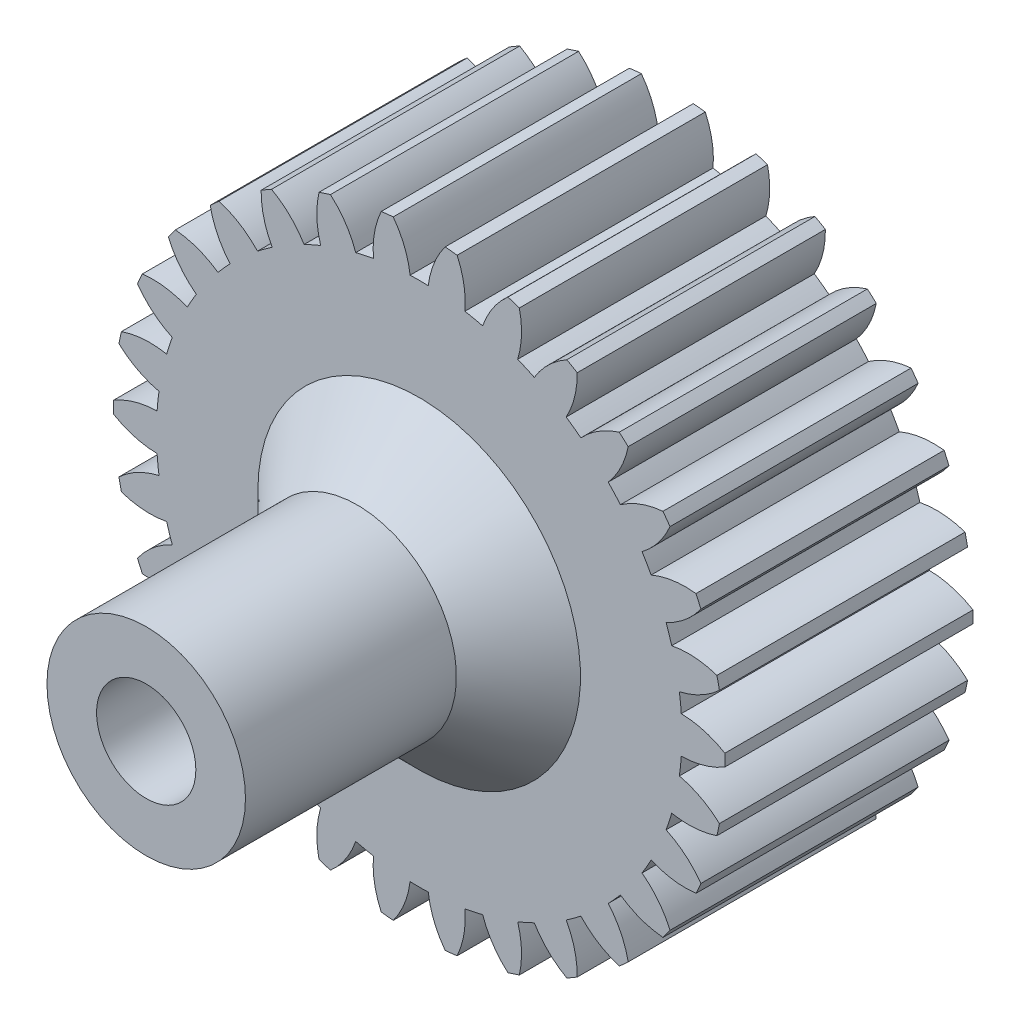
SolidWorks part; units mm, degrees
ref_plane "Front" through (0, 0, 0) normal (0, 0, 1) x (1, 0, 0)
ref_plane "Top" through (0, 0, 0) normal (0, 1, 0) x (1, 0, 0)
ref_plane "Right" through (0, 0, 0) normal (1, 0, 0) x (0, 0, -1)
sketch "Эскиз1" plane through (0, 0, 0) normal (0, 0, 1) x (1, 0, 0)
  circle A0 centre (0, 0) radius 10.5875 construction
  circle A1 centre (0, 0) radius 11.5 construction
  circle A2 centre (0, 0) radius 12.32
  circle A3 centre (0, 0) radius 10.805 construction
  dimension "D1" = 21.175
  dimension "D2" = 23
  dimension "D3" = 24.64
  dimension "D4" = 21.61
extrude "Бобышка-Вытянуть1" add sketch "Эскиз1" along normal mid plane 10
sketch "Эскиз2" plane through (0, 0, 5) normal (0, 0, 1) x (1, 0, 0)
  line L0 (-0.9448, 15.1928) -> (0, 0) construction
  line L1 (-0.7321, 11.7723) -> (-4.9391, 9.6101) construction
  line L2 (-0.6, 11.4843) -> (0.6, 11.4843) construction
  line L3 (0, 0) -> (0, 12.32) construction
  circle A0 centre (0, 0) radius 12.32 construction
  circle A1 centre (0, 0) radius 10.805 construction
  arc A2 (-1.4587, 12.7367) -> (-0.3658, 10.5812) centre (-3.8896, 10.1495) cw
  circle A3 centre (0, 0) radius 10.5875 construction
  circle A4 centre (0, 0) radius 11.5 construction
  arc A5 (1.4587, 12.7367) -> (0.3658, 10.5812) centre (3.8896, 10.1495) ccw
  arc A6 (-0.3658, 10.5812) -> (0.3658, 10.5812) centre (0, 0) cw
  circle A8 centre (0, 0) radius 12.82
  arc A9 (1.4587, 12.7367) -> (-1.4587, 12.7367) centre (0, 0) ccw
  point P3 (-0.7321, 11.7723)
  dimension "D1" = 0.525
  dimension "D2" = 1.2
  dimension "D3" = 4.7301
  dimension "D4" = 1.18
  dimension "D5" = 0.5
sketch "Эскиз4" plane through (0, 0, 0) normal (0, 1, 0) x (1, 0, 0)
  line L0 (0, 5) -> (0, -5)
  line L1 (12.32, 5) -> (-12.32, 5) construction
  line L3 (-12.32, -5) -> (12.32, -5) construction
  line L4 (0, -50) -> (0, 50) construction
  dimension "D1" = 0
curve "Кривая1"
sketch "Эскиз5" plane through (0, 0, -5) normal (0, 0, 1) x (1, 0, 0)
  line L0 (-0.9448, 15.1928) -> (0, 0) construction
  line L1 (-0.7321, 11.7723) -> (-4.9391, 9.6101) construction
  line L2 (-0.6, 11.4843) -> (0.6, 11.4843) construction
  line L3 (0, 0) -> (0, 12.32) construction
  arc A2 (-1.4587, 12.7367) -> (-0.3658, 10.5812) centre (-3.8896, 10.1495) cw
  arc A5 (1.4587, 12.7367) -> (0.3658, 10.5812) centre (3.8896, 10.1495) ccw
  arc A6 (-0.3658, 10.5812) -> (0.3658, 10.5812) centre (0, 0) cw
  arc A9 (1.4587, 12.7367) -> (-1.4587, 12.7367) centre (0, 0) ccw
  point P3 (-0.7321, 11.7723)
loft "Вырез-По сечениям1" cut profiles "Эскиз5", "Эскиз2" connector at (1.4587, 12.7367, -5) connector at (1.4587, 12.7367, 5)
pattern_circular "Круговой массив1" count 30 over 360 about axis through (0, 0, 5) along (0, 0, -1) of "Вырез-По сечениям1"
sketch "Эскиз6" plane through (0, 0, 5) normal (0, 0, 1) x (1, 0, 0)
  circle A0 centre (0, 0) radius 4
  dimension "D1" = 8
extrude "Бобышка-Вытянуть2" add sketch "Эскиз6" along normal blind 11
sketch "Эскиз7" plane through (0, 0, 16) normal (0, 0, 1) x (1, 0, 0)
  circle A0 centre (0, 0) radius 2
  dimension "D1" = 4
extrude "Вырез-Вытянуть1" cut sketch "Эскиз7" against normal blind 3
sketch "Эскиз8" plane through (0, 0, 13) normal (0, 0, 1) x (1, 0, 0)
  line L0 (-1.2639, 1.55) -> (1.2639, 1.55)
  circle A0 centre (0, 0) radius 2 construction
  circle M2 centre (0, 0) radius 2
  dimension "D1" = 1.55
extrude "Вырез-Вытянуть2" cut sketch "Эскиз8" against normal blind 7 and the other way through all contours L0 M2 region at (0, -0.1142, 13)
sketch "Эскиз10" plane through (0, 0, 0) normal (0, 1, 0) x (1, 0, 0)
  line L0 (4, -7.5) -> (6.5, -5)
  line L1 (4, -16) -> (4, -5) construction
  line L3 (6.5, -5) -> (4, -5)
  line L4 (4, -5) -> (4, -7.5)
  line L5 (2.5578, -5) -> (3.5758, -5) construction
  line L6 (6.5154, -5) -> (8.062, -5) construction
  line L7 (0, 5.8944) -> (0, -16.2605) construction
  dimension "D1" = 2.5
revolve "Повернуть1" add sketch "Эскиз10" angle 360 about L7
